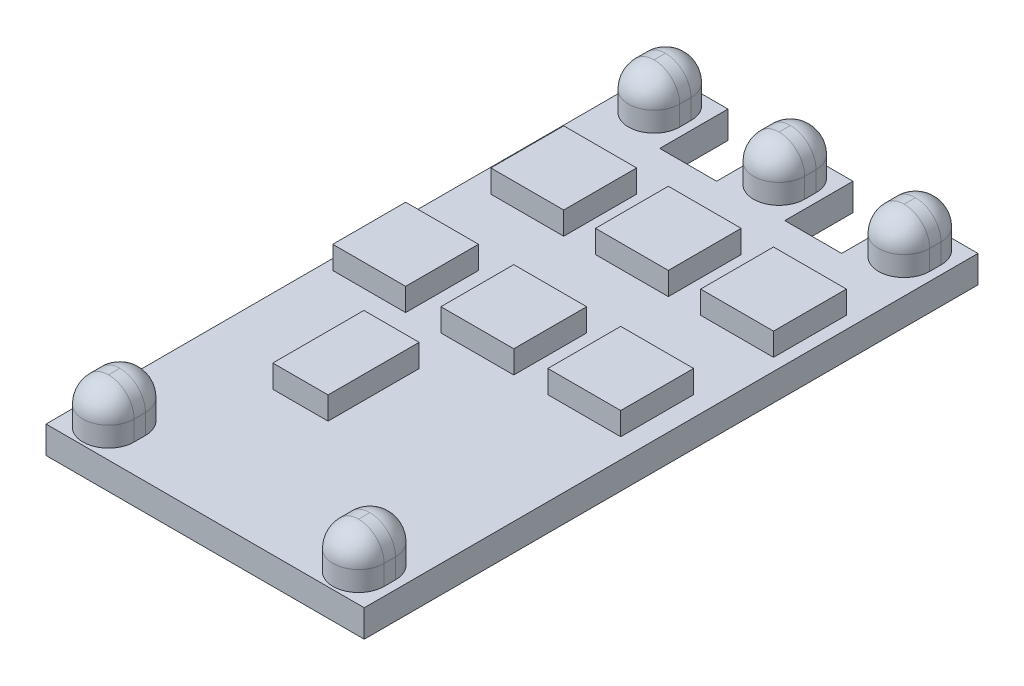
SolidWorks part; units mm, degrees
ref_plane "Front Plane" through (0, 0, 0) normal (0, 0, 1) x (1, 0, 0)
ref_plane "Top Plane" through (0, 0, 0) normal (0, 1, 0) x (1, 0, 0)
ref_plane "Right Plane" through (0, 0, 0) normal (1, 0, 0) x (0, 0, -1)
sketch "Sketch1" plane through (0, 0, 0) normal (0, 1, 0) x (1, 0, 0)
  line L0 (0, 21.6721) -> (0, -24.4888) construction
  line L1 (-7, 12) -> (7, 12)
  line L2 (-7, 12) -> (-7, -12)
  line L3 (-7, -12) -> (7, -12)
  line L4 (7, 12) -> (7, -12)
  line L5 (-7, 12) -> (7, -12) construction
  line L6 (-7, -12) -> (7, 12) construction
  line L8 (-1.5, 15) -> (1.5, 15)
  line L9 (-1.5, 15) -> (-1.5, 12)
  line L10 (-1.5, 12) -> (1.5, 12)
  line L11 (1.5, 15) -> (1.5, 12)
  line L12 (-1.5, 15) -> (1.5, 12) construction
  line L13 (-1.5, 12) -> (1.5, 15) construction
  line L14 (-7, 12) -> (-4, 12)
  line L15 (-7, 12) -> (-7, 15)
  line L16 (-7, 15) -> (-4, 15)
  line L17 (-4, 12) -> (-4, 15)
  line L18 (7, 12) -> (4, 12)
  line L19 (7, 12) -> (7, 15)
  line L20 (7, 15) -> (4, 15)
  line L21 (4, 12) -> (4, 15)
  point P0 (0, 0)
  point P7 (0, 13.5)
  dimension "D1" = 24
  dimension "D2" = 14
  dimension "D3" = 3
  dimension "D4" = 3
extrude "PCB" add sketch "Sketch1" along normal blind 1.2 contours L4 L1 L2 L3 | L1 L17 L16 L15 | L11 L8 L9 L1 | L21 L1 L19 L20 region at (-5.5, 0, -13.5) region at (0, 0, 0) region at (0, 0, -13.5) region at (5.5, 0, -13.5)
sketch "Sketch5" plane through (0, 1.2, 0) normal (0, 1, 0) x (1, 0, 0)
  line L0 (-7, 12) -> (7, 12) construction
  line L1 (-7, 15) -> (-7, -12) construction
  line L2 (7, 15) -> (7, -12) construction
  line L3 (-4, 12) -> (-1.5, 12) construction
  line L4 (-5.5, 15) -> (-5.5, 12) construction
  line L5 (-7, 15) -> (-4, 15) construction
  line L6 (-7, 13.5) -> (7, 13.5) construction
  line L7 (0, 15) -> (0, 12) construction
  line L8 (-1.5, 15) -> (1.5, 15) construction
  line L9 (5.5, 15) -> (5.5, 12) construction
  line L10 (7, 15) -> (4, 15) construction
  line L11 (-5.5, 13.25) -> (-5.5, 13.75) construction
  line L12 (-6.625, 13.25) -> (-6.625, 13.75)
  line L13 (-4.375, 13.25) -> (-4.375, 13.75)
  line L14 (0, 13.75) -> (0, 13.25) construction
  line L15 (1.125, 13.75) -> (1.125, 13.25)
  line L16 (-1.125, 13.75) -> (-1.125, 13.25)
  line L17 (5.5, 13.75) -> (5.5, 13.25) construction
  line L18 (6.625, 13.75) -> (6.625, 13.25)
  line L19 (4.375, 13.75) -> (4.375, 13.25)
  line L20 (-4, 12) -> (-4, 15) construction
  line L21 (-7, -12) -> (7, -12)
  line L22 (-7, -12) -> (-7, -9)
  line L23 (-7, -9) -> (7, -9)
  line L24 (7, -12) -> (7, -9)
  line L25 (-7, -9) -> (-4, -9)
  line L26 (-7, -9) -> (-7, -12)
  line L27 (-7, -12) -> (-4, -12)
  line L28 (-4, -9) -> (-4, -12)
  line L29 (-5.5, -9) -> (-5.5, -12) construction
  line L30 (-5.5, -10.25) -> (-5.5, -10.75) construction
  line L31 (-4.375, -10.25) -> (-4.375, -10.75)
  line L32 (-6.625, -10.25) -> (-6.625, -10.75)
  line L33 (0, -9) -> (0, -12) construction
  line L34 (5.5, -10.25) -> (5.5, -10.75) construction
  line L35 (4.375, -10.25) -> (4.375, -10.75)
  line L36 (6.625, -10.25) -> (6.625, -10.75)
  arc A0 (-6.625, 13.25) -> (-4.375, 13.25) centre (-5.5, 13.25) ccw
  arc A1 (-4.375, 13.75) -> (-6.625, 13.75) centre (-5.5, 13.75) ccw
  arc A2 (1.125, 13.75) -> (-1.125, 13.75) centre (0, 13.75) ccw
  arc A3 (-1.125, 13.25) -> (1.125, 13.25) centre (0, 13.25) ccw
  arc A4 (6.625, 13.75) -> (4.375, 13.75) centre (5.5, 13.75) ccw
  arc A5 (4.375, 13.25) -> (6.625, 13.25) centre (5.5, 13.25) ccw
  arc A6 (-4.375, -10.25) -> (-6.625, -10.25) centre (-5.5, -10.25) ccw
  arc A7 (-6.625, -10.75) -> (-4.375, -10.75) centre (-5.5, -10.75) ccw
  arc A8 (4.375, -10.25) -> (6.625, -10.25) centre (5.5, -10.25) cw
  arc A9 (6.625, -10.75) -> (4.375, -10.75) centre (5.5, -10.75) cw
  point P14 (-5.5, 13.5)
  point P25 (-5.5, 13.5)
  point P32 (0, 13.5)
  point P39 (5.5, 13.5)
  point P57 (-5.5, -10.5)
  point P66 (5.5, -10.5)
  dimension "D1" = 2.25
  dimension "D2" = 0.5
  dimension "D3" = 3
extrude "Solder joints" add sketch "Sketch5" along normal blind 2 contours L13 A1 L12 A0 | L16 A3 L15 A2 | L19 A5 L18 A4 | L32 A7 L31 A6 | A9 L36 A8 L35 region at (-5.5, 1.2, -13.5) region at (0, 1.2, -13.5) region at (5.5, 1.2, -13.5) region at (-5.5, 1.2, 10.5) region at (5.5, 1.2, 10.5)
fillet "Solder fillets" radius 1.125 20 edges at (-5.5, 3.2, 9.125) (-4.375, 3.2, 10.5) (-5.5, 3.2, 11.875) (-6.625, 3.2, 10.5) (4.375, 3.2, 10.5) (5.5, 3.2, 9.125) (6.625, 3.2, 10.5) (5.5, 3.2, 11.875) (5.5, 3.2, -14.875) (6.625, 3.2, -13.5) (5.5, 3.2, -12.125) (4.375, 3.2, -13.5) (0, 3.2, -14.875) (1.125, 3.2, -13.5) (0, 3.2, -12.125) (-1.125, 3.2, -13.5) (-5.5, 3.2, -12.125) (-6.625, 3.2, -13.5) (-5.5, 3.2, -14.875) (-4.375, 3.2, -13.5)
sketch "Sketch2" plane through (0, 1.2, 0) normal (0, 1, 0) x (1, 0, 0)
  line L1 (-5.9719, 9.747) -> (-2.7662, 9.747)
  line L2 (-5.9719, 9.747) -> (-5.9719, 6.5413)
  line L3 (-5.9719, 6.5413) -> (-2.7662, 6.5413)
  line L4 (-2.7662, 9.747) -> (-2.7662, 6.5413)
  line L5 (-1.3702, 9.747) -> (1.8355, 9.747)
  line L6 (-1.3702, 9.747) -> (-1.3702, 6.5413)
  line L7 (-1.3702, 6.5413) -> (1.8355, 6.5413)
  line L8 (1.8355, 9.747) -> (1.8355, 6.5413)
  line L9 (3.2574, 9.747) -> (6.4631, 9.747)
  line L10 (3.2574, 9.747) -> (3.2574, 6.5413)
  line L11 (3.2574, 6.5413) -> (6.4631, 6.5413)
  line L12 (6.4631, 9.747) -> (6.4631, 6.5413)
  line L13 (-3.335, 3.3614) -> (-6.5407, 3.3614)
  line L14 (-3.335, 3.3614) -> (-3.335, 0.1557)
  line L15 (-3.335, 0.1557) -> (-6.5407, 0.1557)
  line L16 (-6.5407, 3.3614) -> (-6.5407, 0.1557)
  line L17 (-1.7838, 3.3614) -> (1.4219, 3.3614)
  line L18 (-1.7838, 3.3614) -> (-1.7838, 0.1557)
  line L19 (-1.7838, 0.1557) -> (1.4219, 0.1557)
  line L20 (1.4219, 3.3614) -> (1.4219, 0.1557)
  line L21 (2.9213, 3.3614) -> (6.1271, 3.3614)
  line L22 (2.9213, 3.3614) -> (2.9213, 0.1557)
  line L23 (2.9213, 0.1557) -> (6.1271, 0.1557)
  line L24 (6.1271, 3.3614) -> (6.1271, 0.1557)
  line L25 (-3.335, -1.6799) -> (-0.9048, -1.6799)
  line L26 (-3.335, -1.6799) -> (-3.335, -5.687)
  line L27 (-3.335, -5.687) -> (-0.9048, -5.687)
  line L28 (-0.9048, -1.6799) -> (-0.9048, -5.687)
extrude "Top components" add sketch "Sketch2" along normal blind 1
sketch "Sketch3" plane through (0, 0, 0) normal (0, -1, 0) x (1, 0, 0)
  line L1 (-2.7921, 0) -> (1.2409, 0)
  line L2 (-2.7921, 0) -> (-2.7921, 4.0583)
  line L3 (-2.7921, 4.0583) -> (1.2409, 4.0583)
  line L4 (1.2409, 0) -> (1.2409, 4.0583)
  line L5 (-5.8944, -3.9818) -> (-2.7921, -3.9818)
  line L6 (-5.8944, -3.9818) -> (-5.8944, -6.9032)
  line L7 (-5.8944, -6.9032) -> (-2.7921, -6.9032)
  line L8 (-2.7921, -3.9818) -> (-2.7921, -6.9032)
  line L9 (-1.3185, -3.9818) -> (1.4995, -3.9818)
  line L10 (-1.3185, -3.9818) -> (-1.3185, -6.9032)
  line L11 (-1.3185, -6.9032) -> (1.4995, -6.9032)
  line L12 (1.4995, -3.9818) -> (1.4995, -6.9032)
  line L13 (3.0765, -3.9818) -> (5.9461, -3.9818)
  line L14 (3.0765, -3.9818) -> (3.0765, -6.9032)
  line L15 (3.0765, -6.9032) -> (5.9461, -6.9032)
  line L16 (5.9461, -3.9818) -> (5.9461, -6.9032)
  line L17 (3.516, 9.4874) -> (5.3515, 9.4874)
  line L18 (3.516, 9.4874) -> (3.516, 6.3592)
  line L19 (3.516, 6.3592) -> (5.3515, 6.3592)
  line L20 (5.3515, 9.4874) -> (5.3515, 6.3592)
extrude "Bottom components" add sketch "Sketch3" along normal blind 1
ref_plane "Motor wires plane" through (0, 0, -13.5) normal (0, 0, -1) x (-1, 0, 0)
ref_plane "Control wires plane" through (0, 0, 10.5) normal (0, 0, 1) x (1, 0, 0)
sketch "Motor wire locations" plane through (0, 0, -13.5) normal (0, 0, -1) x (-1, 0, 0)
  line L0 (7, 1.2) -> (4, 1.2) construction
  line L1 (1.5, 1.2) -> (-1.5, 1.2) construction
  line L2 (-7, 1.2) -> (-4, 1.2) construction
  line L3 (7, 1.2) -> (4, 1.2)
  line L4 (1.5, 1.2) -> (-1.5, 1.2)
  line L5 (-7, 1.2) -> (-4, 1.2)
  line L6 (-7, 2.7) -> (-4, 1.2) construction
  line L7 (-7, 1.2) -> (-4, 1.2)
  line L8 (-7, 1.2) -> (-7, 2.7)
  line L9 (-7, 2.7) -> (-4, 2.7)
  line L10 (-4, 1.2) -> (-4, 2.7)
  line L11 (-1.5, 2.7) -> (1.5, 1.2) construction
  line L12 (-1.5, 1.2) -> (1.5, 1.2)
  line L13 (-1.5, 1.2) -> (-1.5, 2.7)
  line L14 (-1.5, 2.7) -> (1.5, 2.7)
  line L15 (1.5, 1.2) -> (1.5, 2.7)
  line L16 (4, 1.2) -> (7, 1.2)
  line L17 (4, 1.2) -> (4, 2.7)
  line L18 (4, 2.7) -> (7, 2.7)
  line L19 (7, 1.2) -> (7, 2.7)
  line L20 (4, 2.7) -> (7, 1.2) construction
  point P9 (-5.5, 1.95)
  point P14 (0, 1.95)
  point P15 (5.5, 1.95)
  dimension "D1" = 1.5
sketch "Control wire locations" plane through (0, 0, 10.5) normal (0, 0, 1) x (1, 0, 0)
  line L0 (-4, 1.2) -> (-4, 2.7) construction
  line L1 (-7, 1.2) -> (-4, 1.2)
  line L2 (-7, 1.2) -> (-7, 2.7)
  line L3 (-7, 2.7) -> (-4, 2.7)
  line L4 (-4, 1.2) -> (-4, 2.7)
  line L5 (-4, 2.7) -> (-7, 2.7) construction
  line L6 (-7, 1.2) -> (-4, 2.7) construction
  line L7 (0, 4.0612) -> (0, -2.6256) construction
  line L8 (-7, 1.2) -> (-7, 2.7) construction
  line L9 (-7, 1.2) -> (-4, 1.2) construction
  line L10 (7, 1.2) -> (4, 2.7) construction
  line L11 (4, 1.2) -> (4, 2.7)
  line L12 (7, 1.2) -> (4, 1.2)
  line L13 (7, 1.2) -> (7, 2.7)
  line L14 (7, 2.7) -> (4, 2.7)
  point P4 (5.5, 1.95)
  point P9 (-5.5, 1.95)
  point P11 (0, 0)
  point P16 (-7, 1.3176)
other "A" parameters "Diameter"=1.5, "StubLength"=3
ref_axis "Axis1" through (5.5, 1.95, -23.5) along (0, 0, 1)
other "B" parameters "Diameter"=1.5, "StubLength"=3
ref_axis "Axis2" through (0, 1.95, -23.5) along (0, 0, 1)
other "C" parameters "Diameter"=1.5, "StubLength"=3
ref_axis "Axis3" through (-5.5, 1.95, -23.5) along (0, 0, 1)
other "NEG" parameters "Diameter"=1.5, "StubLength"=3
ref_axis "Axis4" through (-5.5, 1.95, 20.5) along (0, 0, -1)
other "POS" parameters "Diameter"=1.5, "StubLength"=3
ref_axis "Axis5" through (5.5, 1.95, 20.5) along (0, 0, -1)
